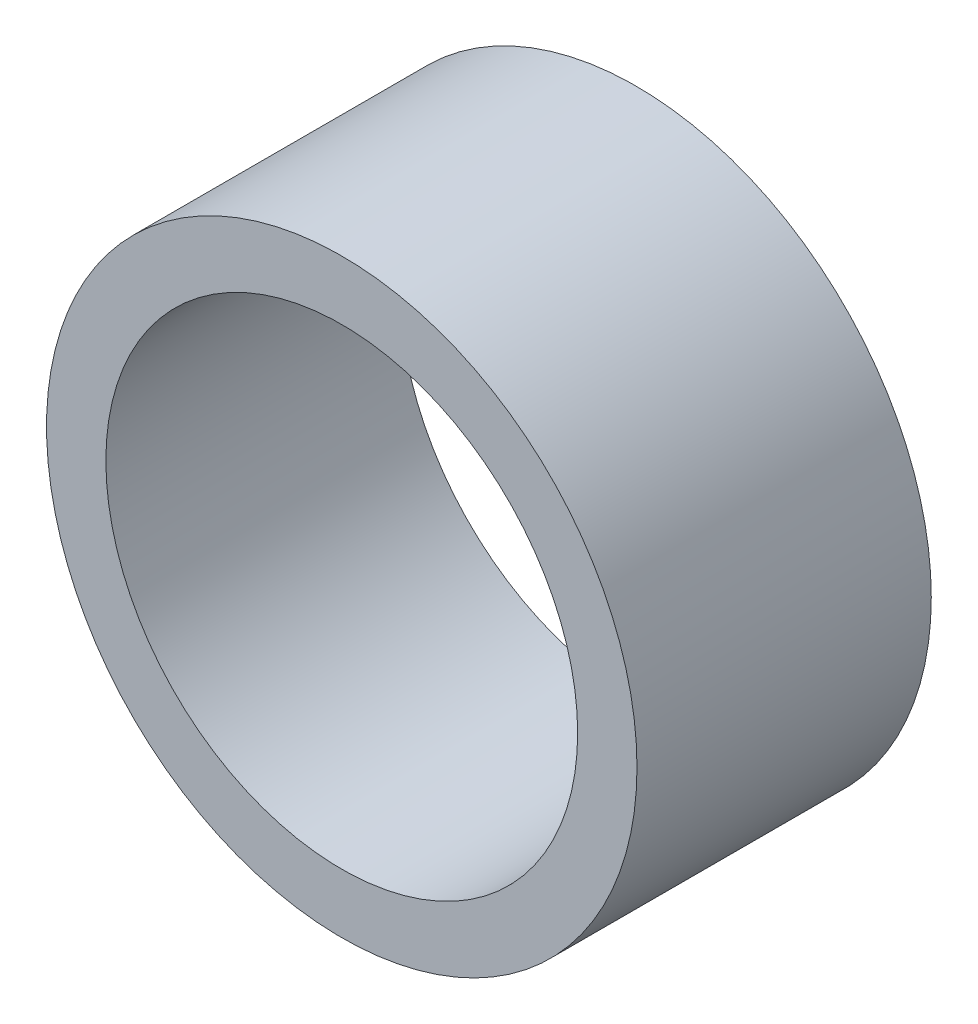
SolidWorks part; units mm, degrees
ref_plane "Front Plane" through (0, 0, 0) normal (0, 0, 1) x (1, 0, 0)
ref_plane "Top Plane" through (0, 0, 0) normal (0, 1, 0) x (1, 0, 0)
ref_plane "Right Plane" through (0, 0, 0) normal (1, 0, 0) x (0, 0, -1)
sketch "Sketch1" plane through (0, 0, 0) normal (0, 0, 1) x (1, 0, 0)
  circle A0 centre (0, 0) radius 7.9629
  circle A1 centre (0, 0) radius 6.3627
  dimension "OD" = 15.9258
  dimension "ID" = 12.7254
sketch "Sketch2" plane through (0, 0, 0) normal (1, 0, 0) x (0, 0, -1)
  line L2 (3.9688, 0) -> (-3.9688, 0) construction
  line L4 (-3.9688, -7.9629) -> (-3.9688, 7.9629) construction
  line L5 (-3.9688, -6.3627) -> (3.9688, -6.3627)
  line L6 (3.9688, 6.3627) -> (-3.9688, 6.3627)
  line L7 (3.9688, -7.9629) -> (3.9688, 7.9629) construction
  line L8 (-3.9688, 7.9629) -> (3.9688, 7.9629) construction
  line L9 (-3.9688, -7.9629) -> (3.9688, -7.9629) construction
  line L10 (0, 7.9629) -> (0, -7.9629) construction
  line L11 (0, 6.3627) -> (0, -6.3627) construction
  point P4 (0, -6.3627)
  point P7 (0, 6.3627)
  point P8 (0, 0)
  point P12 (-3.9688, 0)
  point P15 (3.9688, 0)
  point P16 (0, -7.9629)
  point P17 (0, 7.9629)
  dimension "Length" = 7.9375
sketch "Sketch5" plane through (0, 0, 0) normal (0, 0, 1) x (1, 0, 0)
  circle A1 centre (0, 0) radius 6.3627
  circle A2 centre (0, 0) radius 6.3627
  circle A3 centre (0, 0) radius 7.9629
  circle A4 centre (0, 0) radius 7.9629
  dimension "D1" = 0
  dimension "D2" = 0
extrude "Boss-Extrude1" add sketch "Sketch5" along normal up to vertex and the other way up to vertex up to point (0, 0, 3.9688) other way up to point (0, 0, -3.9688)
sketch "Sketch4" plane through (0, 0, 3.9688) normal (0, 0, 1) x (1, 0, 0)
  line L0 (0, 0) -> (-4.4991, 4.4991)
  line L2 (0, -7.9629) -> (0, 7.9629) construction
  circle A1 centre (0, 0) radius 6.3627 construction
  dimension "D1" = 45
equation "\"D1\"= \"Length@Sketch2\""
